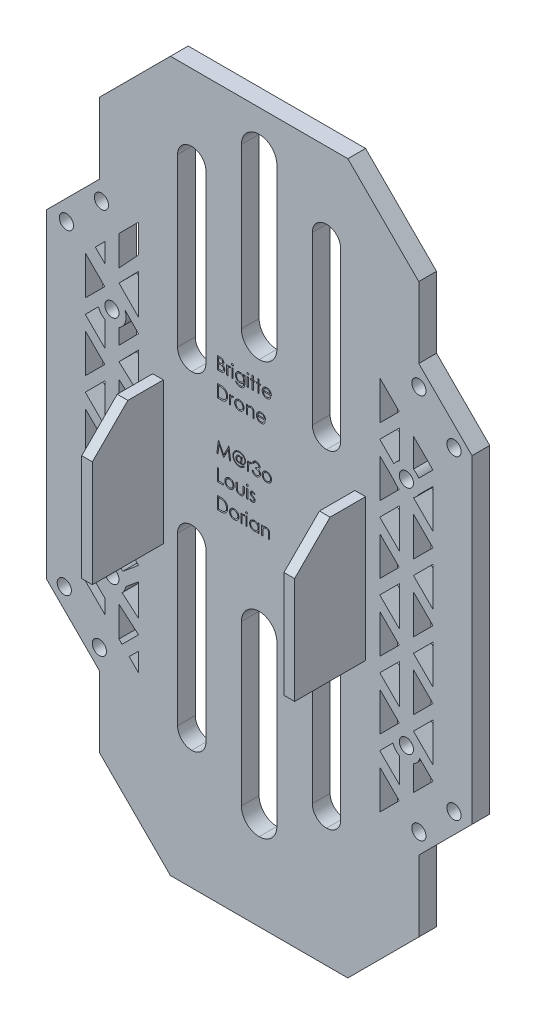
SolidWorks part; units mm, degrees
ref_plane "Plan de face" through (0, 0, 0) normal (0, 0, 1) x (1, 0, 0)
ref_plane "Plan de dessus" through (0, 0, 0) normal (0, 1, 0) x (1, 0, 0)
ref_plane "Plan de droite" through (0, 0, 0) normal (1, 0, 0) x (0, 0, -1)
sketch "Esquisse1" plane through (0, 0, 0) normal (0, 0, 1) x (1, 0, 0)
  line L0 (-41.0719, 30.2056) -> (78.9281, 30.2056)
  line L1 (78.9281, 30.2056) -> (78.9281, -89.7944)
  line L2 (78.9281, -89.7944) -> (-41.0719, -89.7944)
  line L3 (-41.0719, -89.7944) -> (-41.0719, 30.2056)
  dimension "D1" = 120
  dimension "D2" = 120
extrude "Boss.-Extru.2" add sketch "Esquisse1" along normal blind 5
sketch "Esquisse3" plane through (0, 0, 0) normal (0, 0, -1) x (-1, 0, 0)
sketch "Esquisse7" plane through (0, 0, 5) normal (0, 0, 1) x (1, 0, 0)
sketch "Esquisse9" plane through (0, 0, 5) normal (0, 0, 1) x (1, 0, 0)
  line L0 (-41.0719, -89.7944) -> (78.9281, -89.7944) construction
  line L1 (78.9281, -89.7944) -> (78.9281, 30.2056) construction
  circle A0 centre (-22.5719, -64.7944) radius 2
  circle A1 centre (-22.5719, 0.2056) radius 2
  circle A2 centre (60.4281, 0.2056) radius 2
  circle A3 centre (60.4281, -64.7944) radius 2
  dimension "D5" = 4
  dimension "D6" = 4
  dimension "D7" = 4
  dimension "D8" = 4
  dimension "D1" = 83
  dimension "D2" = 83
  dimension "D3" = 18.5
  dimension "D4" = 65
  dimension "D9" = 25
  dimension "D10" = 25
  dimension "D11" = 18.5
chamfer "Chanfrein5" distance 15 angle 45 1 edges at (78.9281, -89.7944, 2.5)
chamfer "Chanfrein6" distance 15 angle 45 1 edges at (78.9281, 30.2056, 2.5)
chamfer "Chanfrein7" distance 15 angle 45 1 edges at (-41.0719, 30.2056, 2.5)
chamfer "Chanfrein8" distance 15 angle 45 1 edges at (-41.0719, -89.7944, 2.5)
sketch "Esquisse21" plane through (0, -89.7944, 0) normal (0, -1, 0) x (-1, 0, 0)
  line L0 (26.0719, -5) -> (26.0719, 0)
  line L1 (26.0719, 0) -> (-63.9281, 0)
  line L2 (-63.9281, 0) -> (-63.9281, -5)
  line L3 (-63.9281, -5) -> (26.0719, -5)
extrude "Boss.-Extru.7" add sketch "Esquisse21" along normal blind 40
sketch "Esquisse22" plane through (0, 30.2056, 0) normal (0, 1, 0) x (1, 0, 0)
  line L0 (63.9281, -5) -> (63.9281, 0)
  line L1 (63.9281, 0) -> (-26.0719, 0) construction
  line L2 (63.9281, 0) -> (-26.0719, 0)
  line L3 (-26.0719, 0) -> (-26.0719, -5)
  line L4 (-26.0719, -5) -> (63.9281, -5)
extrude "Boss.-Extru.8" add sketch "Esquisse22" along normal blind 40
chamfer "Chanfrein23" distance 20 angle 45 4 edges at (-26.0719, -129.7944, 2.5) (63.9281, -129.7944, 2.5) (-26.0719, 70.2056, 2.5) (63.9281, 70.2056, 2.5)
sketch "Esquisse23" plane through (0, 0, 5) normal (0, 0, 1) x (1, 0, 0)
  line L0 (-41.0719, -74.7944) -> (-26.0719, -89.7944) construction
  line L1 (-26.0719, 30.2056) -> (-41.0719, 15.2056) construction
  line L3 (78.9281, 15.2056) -> (63.9281, 30.2056) construction
  line L5 (63.9281, -89.7944) -> (78.9281, -74.7944) construction
  circle A0 centre (-35.9963, -74.2132) radius 2
  circle A1 centre (-26.0968, -84.1127) radius 2
  circle A2 centre (-25.5241, 25.0966) radius 2
  circle A3 centre (-35.3901, 15.1637) radius 2
  circle A4 centre (63.9532, 24.5237) radius 2
  circle A5 centre (73.8527, 14.6242) radius 2
  circle A6 centre (63.9532, -84.1124) radius 2
  circle A7 centre (73.8527, -74.2129) radius 2
  dimension "D3" = 4
  dimension "D4" = 4
  dimension "D6" = 4
  dimension "D7" = 4
  dimension "D10" = 5.6818
  dimension "D15" = 4
  dimension "D16" = 4
  dimension "D19" = 14
  dimension "D23" = 4
  dimension "D24" = 4
  dimension "D1" = 4
  dimension "D2" = 4
  dimension "D5" = 14
  dimension "D8" = 14
  dimension "D9" = 4
  dimension "D11" = 5.682
  dimension "D12" = 5.109
  dimension "D13" = 14
  dimension "D14" = 4
  dimension "D17" = 4
  dimension "D18" = 5.682
  dimension "D20" = 4
  dimension "D21" = 5.682
  dimension "D22" = 4
extrude "Enlèv. mat.-Extru.1" cut sketch "Esquisse23" against normal blind 10
sketch "Esquisse24" plane through (0, 0, 5) normal (0, 0, 1) x (1, 0, 0)
  line L0 (63.9281, -89.7944) -> (78.9281, -74.7944) construction
  circle A0 centre (63.5389, -84.5268) radius 2.5407
  circle A1 centre (73.4383, -74.6273) radius 2.5147
  dimension "D1" = 4
  dimension "D2" = 4
  dimension "D3" = 14
  dimension "D4" = 5.282
sketch "Sketch1" plane through (0, 0, 5) normal (0, 0, 1) x (1, 0, 0)
  line L1 (13.9281, -107.7944) -> (23.9281, -107.7944)
  line L2 (13.9281, -107.7944) -> (13.9281, -52.7944)
  line L3 (13.9281, -52.7944) -> (23.9281, -52.7944)
  line L4 (23.9281, -107.7944) -> (23.9281, -52.7944)
  line L6 (43.9281, -129.7944) -> (-6.0719, -129.7944) construction
  dimension "D1" = 10
  dimension "D2" = 55
  dimension "D3" = 40
  dimension "D4" = 22
extrude "Cut-Extrude2" cut sketch "Sketch1" against normal blind 5 contours L2 L1 L4 L3
fillet "Fillet2" radius 5 1 edges at (13.9281, -107.7944, 2.5)
fillet "Fillet3" radius 5 3 edges at (13.9281, -52.7944, 2.5) (23.9281, -52.7944, 2.5) (23.9281, -107.7944, 2.5)
sketch "Sketch2" plane through (0, 0, 5) normal (0, 0, 1) x (1, 0, 0)
  line L0 (23.9281, -102.7944) -> (23.9281, -57.7944) construction
  line L1 (41.9281, -96.2103) -> (33.9281, -96.2103)
  line L2 (41.9281, -96.2103) -> (41.9281, -41.2103)
  line L3 (41.9281, -41.2103) -> (33.9281, -41.2103)
  line L4 (33.9281, -96.2103) -> (33.9281, -41.2103)
  line L5 (13.9281, -102.7944) -> (13.9281, -57.7944) construction
  line L6 (3.9281, -96.2103) -> (-4.0719, -96.2103)
  line L7 (3.9281, -96.2103) -> (3.9281, -41.2103)
  line L8 (3.9281, -41.2103) -> (-4.0719, -41.2103)
  line L9 (-4.0719, -96.2103) -> (-4.0719, -41.2103)
  dimension "D1" = 10
  dimension "D2" = 10
  dimension "D3" = 8
  dimension "D4" = 8
  dimension "D5" = 55
  dimension "D6" = 55
sketch "Sketch3" plane through (0, 0, 5) normal (0, 0, 1) x (1, 0, 0)
  line L0 (78.9281, -74.7944) -> (78.9281, 15.2056) construction
  line L1 (23.9281, 63.6661) -> (13.9281, 63.6661)
  line L2 (23.9281, 63.6661) -> (23.9281, 8.6661)
  line L3 (23.9281, 8.6661) -> (13.9281, 8.6661)
  line L4 (13.9281, 63.6661) -> (13.9281, 8.6661)
  dimension "D1" = 10
  dimension "D2" = 55
  dimension "D3" = 55
extrude "Cut-Extrude4" cut sketch "Sketch3" against normal blind 5
fillet "Fillet11" radius 5 4 edges at (13.9281, 63.6661, 2.5) (23.9281, 63.6661, 2.5) (23.9281, 8.6661, 2.5) (13.9281, 8.6661, 2.5)
extrude "Cut-Extrude5" cut sketch "Sketch2" against normal blind 8
sketch "Sketch4" plane through (0, 0, 5) normal (0, 0, 1) x (1, 0, 0)
  line L0 (13.9281, 58.6661) -> (13.9281, 13.6661) construction
  line L1 (-4.0719, 51.2056) -> (3.9281, 51.2056)
  line L2 (-4.0719, 51.2056) -> (-4.0719, -3.7944)
  line L3 (-4.0719, -3.7944) -> (3.9281, -3.7944)
  line L4 (3.9281, 51.2056) -> (3.9281, -3.7944)
  line L5 (33.9281, 51.2056) -> (41.9281, 51.2056)
  line L6 (33.9281, 51.2056) -> (33.9281, -3.7944)
  line L7 (33.9281, -3.7944) -> (41.9281, -3.7944)
  line L8 (41.9281, 51.2056) -> (41.9281, -3.7944)
  line L9 (23.9281, 13.6661) -> (23.9281, 58.6661) construction
  line L10 (-6.0719, 70.2056) -> (43.9281, 70.2056) construction
  dimension "D1" = 8
  dimension "D2" = 55
  dimension "D3" = 55
  dimension "D4" = 8
  dimension "D5" = 10
  dimension "D6" = 10
  dimension "D7" = 19
  dimension "D8" = 19
extrude "Cut-Extrude6" cut sketch "Sketch4" against normal blind 8
fillet "Fillet12" radius 4 4 edges at (33.9281, 51.2056, 2.5) (41.9281, 51.2056, 2.5) (41.9281, -3.7944, 2.5) (33.9281, -3.7944, 2.5)
fillet "Fillet13" radius 4 4 edges at (-4.0719, -3.7944, 2.5) (3.9281, -3.7944, 2.5) (-4.0719, 51.2056, 2.5) (3.9281, 51.2056, 2.5)
fillet "Fillet14" radius 4 4 edges at (3.9281, -41.2103, 2.5) (-4.0719, -41.2103, 2.5) (-4.0719, -96.2103, 2.5) (3.9281, -96.2103, 2.5)
fillet "Fillet15" radius 4 4 edges at (41.9281, -96.2103, 2.5) (33.9281, -96.2103, 2.5) (33.9281, -41.2103, 2.5) (41.9281, -41.2103, 2.5)
sketch "Sketch5" plane through (0, 0, 5) normal (0, 0, 1) x (1, 0, 0)
  line L0 (-6.0719, 70.2056) -> (43.9281, 70.2056) construction
  line L1 (-11.0719, -9.7944) -> (-8.0719, -9.7944)
  line L2 (-11.0719, -9.7944) -> (-11.0719, -49.7944)
  line L3 (-11.0719, -49.7944) -> (-8.0719, -49.7944)
  line L4 (-8.0719, -9.7944) -> (-8.0719, -49.7944)
  line L5 (45.9281, -9.7944) -> (48.9281, -9.7944)
  line L6 (45.9281, -9.7944) -> (45.9281, -49.7944)
  line L7 (45.9281, -49.7944) -> (48.9281, -49.7944)
  line L8 (48.9281, -9.7944) -> (48.9281, -49.7944)
  line L9 (-41.0719, 15.2056) -> (-41.0719, -74.7944) construction
  dimension "D1" = 40
  dimension "D2" = 40
  dimension "D3" = 80
  dimension "D4" = 80
  dimension "D5" = 3
  dimension "D6" = 3
  dimension "D7" = 54
  dimension "D8" = 30
extrude "Boss-Extrude1" add sketch "Sketch5" along normal blind 20
chamfer "Chamfer1" distance 10 angle 45 1 edges at (47.4281, -9.7944, 25)
chamfer "Chamfer2" distance 10 angle 45 1 edges at (-9.5719, -9.7944, 25)
extrude "Cut-Extrude7" cut sketch "Esquisse9" against normal blind 10
sketch "Sketch6" plane through (0, 0, 5) normal (0, 0, 1) x (1, 0, 0)
  line L0 (-15.0719, -120.7944) -> (-15.0719, 61.2056)
  line L1 (-26.0719, -109.7944) -> (-6.0719, -129.7944) construction
  line L2 (-6.0719, 70.2056) -> (-26.0719, 50.2056) construction
  line L3 (-30.0719, -85.7944) -> (-30.0719, 26.2056)
  line L4 (-41.0719, -74.7944) -> (-26.0719, -89.7944) construction
  line L5 (-26.0719, 30.2056) -> (-41.0719, 15.2056) construction
  line L6 (-41.0719, 15.2056) -> (-41.0719, -74.7944) construction
  line L7 (-15.0719, 17.2056) -> (-20.5719, 11.2719)
  line L8 (-20.5719, -115.2944) -> (-20.5719, 55.7056)
  line L9 (-24.5719, -53.8095) -> (-24.5719, 126.1905)
  line L10 (-24.5719, -53.8095) -> (-24.5719, -111.2944)
  line L11 (-15.0719, -84.7944) -> (-30.0719, -69.7944)
  line L12 (-15.0719, 25.2056) -> (-30.0719, 10.2056)
  line L13 (-15.0719, 13.2056) -> (-20.5719, 7.5964)
  line L14 (-20.5719, 7.5964) -> (-15.0719, 1.9874)
  line L15 (-20.5719, 7.5964) -> (-15.0719, 7.5964)
  line L16 (-15.0719, -6.0126) -> (-20.5719, -11.6216)
  line L17 (-20.5719, 3.5964) -> (-20.2132, 3.2306)
  line L18 (-19.2957, 2.2949) -> (-15.0719, -2.0126)
  line L19 (-15.0719, -2.0126) -> (-20.5719, -7.6216)
  line L20 (-20.5719, -11.6216) -> (-15.0719, -16.6452)
  line L21 (-20.5719, -15.9374) -> (-15.0719, -20.6452)
  line L22 (-15.0719, -20.6452) -> (-20.5719, -26.0772)
  line L23 (-15.0719, -24.6452) -> (-20.5719, -30.0772)
  line L24 (-20.5719, -30.0772) -> (-15.0719, -35.5772)
  line L25 (-20.5719, -34.0772) -> (-15.0719, -39.5772)
  line L26 (-15.0719, -39.5772) -> (-20.5719, -45.0772)
  line L27 (-20.5719, -49.0772) -> (-15.0719, -43.5772)
  line L28 (-20.5719, -49.0772) -> (-15.0719, -54.5772)
  line L29 (-20.5719, -53.0772) -> (-15.0719, -58.5772)
  line L30 (-15.0719, -58.5772) -> (-19.4924, -62.2416)
  line L31 (-15.0719, -62.5772) -> (-18.6413, -65.536)
  line L32 (-20.5719, -70.7698) -> (-15.0719, -75.5192)
  line L36 (-15.0719, -71.5192) -> (-19.6707, -67.5481)
  line L37 (-15.0719, -75.5192) -> (-19.7096, -80.1568)
  line L38 (-15.0719, -79.5192) -> (-17.7096, -82.1568)
  line L39 (-30.0719, 10.2056) -> (-24.5719, 4.7056)
  line L40 (-27.2435, 13.034) -> (-24.5719, 10.3625)
  line L41 (-24.5719, 4.7056) -> (-30.0719, 4.7056)
  line L43 (-24.5719, 4.7056) -> (-30.0719, -0.7944)
  line L45 (-30.0719, -65.7988) -> (-30.0719, -69.7944)
  line L46 (-30.0719, -4.7944) -> (-24.5719, -4.7944)
  line L47 (-30.0719, -4.7944) -> (-24.5719, -10.2944)
  line L48 (-30.0719, -8.7944) -> (-24.5719, -14.2944)
  line L49 (-24.5719, -14.2944) -> (-30.0719, -14.2944)
  line L50 (-24.5719, -14.2944) -> (-30.0719, -19.7944)
  line L51 (-24.5719, -18.2944) -> (-30.0719, -23.7944)
  line L52 (-30.0719, -23.7944) -> (-24.5719, -23.7944)
  line L53 (-30.0719, -23.7944) -> (-24.5719, -29.2944)
  line L54 (-30.0719, -27.7944) -> (-24.5719, -33.2944)
  line L55 (-24.5719, -33.2944) -> (-30.0719, -33.2944)
  line L56 (-24.5719, -33.2944) -> (-30.0719, -38.9521)
  line L57 (-24.5719, -37.2944) -> (-30.0719, -42.9521)
  line L58 (-30.0719, -42.9521) -> (-24.5719, -42.9521)
  line L59 (-30.0719, -42.9521) -> (-24.5719, -48.2988)
  line L60 (-30.0719, -46.9521) -> (-24.5719, -52.2988)
  line L61 (-24.5719, -52.2988) -> (-30.0719, -52.2988)
  line L62 (-24.5719, -52.2988) -> (-30.0719, -57.7988)
  line L63 (-24.5719, -56.2988) -> (-30.0719, -61.7988)
  line L64 (-30.0719, -61.7988) -> (-24.5719, -61.7988)
  line L66 (-30.0719, -65.7988) -> (-24.5719, -71.2988)
  line L67 (-30.0719, -61.7988) -> (-26.5352, -65.3356)
  line L68 (-24.5719, -75.2988) -> (-24.5697, -75.2966)
  line L69 (-30.0719, -4.7944) -> (-26.3592, -1.0816)
  line L70 (-30.0719, -69.7944) -> (-26.5697, -73.2966)
  circle A0 centre (-22.5719, -64.7944) radius 4
  circle A4 centre (-22.5719, 0.2056) radius 4
  dimension "D6" = 8
  dimension "D32" = 8
  dimension "D1" = 15
  dimension "D2" = 11
  dimension "D3" = 8
  dimension "D4" = 4
  dimension "D7" = 4
  dimension "D8" = 36
  dimension "D9" = 16
  dimension "D10" = 36
  dimension "D11" = 16
  dimension "D12" = 4
  dimension "D13" = 4
  dimension "D14" = 4
  dimension "D15" = 4
  dimension "D16" = 4
  dimension "D17" = 4
  dimension "D18" = 4
  dimension "D19" = 4
  dimension "D20" = 4
  dimension "D21" = 4
  dimension "D22" = 4
  dimension "D23" = 4
  dimension "D24" = 4
  dimension "D25" = 0
  dimension "D26" = 4
  dimension "D27" = 4
  dimension "D28" = 4
  dimension "D29" = 9.5
  dimension "D30" = 4
  dimension "D31" = 0
  dimension "D33" = 4
  dimension "D34" = 5.5
  dimension "D35" = 4
  dimension "D36" = 5.5
  dimension "D37" = 4
  dimension "D38" = 4
  dimension "D39" = 5.5
  dimension "D40" = 4
  dimension "D41" = 4
  dimension "D42" = 4
  dimension "D43" = 4
  dimension "D44" = 4
  dimension "D45" = 4
  dimension "D46" = 4
  dimension "D47" = 4
  dimension "D48" = 4
  dimension "D49" = 4
  dimension "D50" = 4
  dimension "D51" = 4
  dimension "D52" = 5.5
  dimension "D53" = 5.5
  dimension "D54" = 11
  dimension "D55" = 5.2752
extrude "Cut-Extrude8" cut sketch "Sketch6" against normal blind 10 contours L0 L38 L11 | L37 L32 L8 L11 | A0 L36 L0 L31 | A0 L30 L29 L8 | L27 L28 L0 | L26 L25 L8 | L23 L24 L0 | L22 L21 L8 | L16 L20 L0 | A4 L8 L19 L18 | L15 L14 L0 | L13 L15 L0 | L0 L12 L8 L7 | L12 L40 L9 region at (-15.9511, -82.1568, 5) region at (-18.6967, -75.6505, 5) region at (-16.6873, -67.0376, 5) region at (-18.6818, -58.1104, 5) region at (-16.9053, -49.0772, 5) region at (-18.7386, -39.5772, 5) region at (-16.9053, -30.0999, 5) region at (-18.7386, -20.8866, 5) region at (-16.9053, -11.4265, 5) region at (-18.288, -2.9591, 5) region at (-16.9053, 5.7267, 5) region at (-16.9053, 9.4661, 5) region at (-17.8461, 18.322, 5) region at (-25.4625, 13.034, 5)
sketch "Sketch7" plane through (0, 0, 5) normal (0, 0, 1) x (1, 0, 0)
extrude "Cut-Extrude9" cut sketch "Sketch6<3>" against normal blind 10 from offset 0 contours L12 L40 L9 | L41 L39 L3 | L43 L41 L3 | A4 L69 L46 L9 | L46 L47 L9 | L49 L48 L3 | L50 L49 L3 | L51 L52 L9 | L52 L53 L9 | L55 L54 L3 | L56 L55 L3 | L57 L58 L9 | L58 L59 L9 | L61 L60 L3 | L62 L61 L3 | A0 L10 L63 L64 | A0 L64 L67 | L10 L11 region at (-27.3219, -70.5466, 5) region at (-26.4228, -59.9472, 5) region at (-27.4757, -62.8923, 5) region at (-28.2386, -54.1321, 5) region at (-28.2386, -50.5165, 5) region at (-26.4053, -44.7343, 5) region at (-26.4053, -41.0662, 5) region at (-28.2386, -35.1803, 5) region at (-28.2386, -31.4611, 5) region at (-26.4053, -25.6277, 5) region at (-26.4053, -21.9611, 5) region at (-26.8378, -3.5511, 5) region at (-28.2386, -16.1277, 5) region at (-26.4053, -6.6277, 5) region at (-28.2386, -12.4611, 5) region at (-28.2386, 6.5389, 5) region at (-28.2386, 2.8723, 5) region at (-25.4625, 13.034, 5)
sketch "Sketch6<3>" plane through (0, 0, 5) normal (0, 0, 1) x (1, 0, 0) same geometry as "Sketch6"
sketch "Sketch9" plane through (0, 0, 5) normal (0, 0, 1) x (1, 0, 0)
  line L0 (78.9281, -74.7944) -> (78.9281, 15.2056) construction
  line L1 (58.4281, -60.2944) -> (52.9281, -60.2944)
  line L2 (43.9281, -129.7944) -> (63.9281, -109.7944) construction
  line L3 (62.4281, -111.2944) -> (62.4281, 51.7056)
  line L4 (63.9281, 50.2056) -> (43.9281, 70.2056) construction
  line L5 (58.4281, -115.2944) -> (58.4281, 55.7056)
  line L6 (67.9281, -85.7944) -> (67.9281, 26.2056)
  line L7 (63.9281, -89.7944) -> (78.9281, -74.7944) construction
  line L8 (78.9281, 15.2056) -> (63.9281, 30.2056) construction
  line L9 (52.9281, -120.7944) -> (52.9281, 61.2056)
  line L10 (52.9281, -120.7944) -> (52.9281, -84.7944)
  line L11 (67.9281, -85.7944) -> (67.9281, -69.7944)
  line L12 (52.9281, -84.7944) -> (67.9281, -69.7944)
  line L13 (52.9281, -79.2944) -> (58.4281, -79.2944)
  line L14 (58.4281, -79.2944) -> (52.9281, -73.7944)
  line L15 (52.9281, -69.7944) -> (58.4281, -75.2944)
  line L16 (52.9281, -69.7944) -> (58.4281, -69.7944)
  line L17 (52.9281, -69.7944) -> (58.4281, -64.2944)
  line L18 (52.9281, -65.7944) -> (58.4281, -60.2944)
  line L19 (58.4281, -60.2944) -> (52.9281, -54.7944)
  line L20 (52.9281, -50.7944) -> (58.4281, -56.2944)
  line L21 (52.9281, -50.7944) -> (58.4281, -50.7944)
  line L22 (52.9281, -50.7944) -> (58.4281, -45.2944)
  line L23 (52.9281, -46.7944) -> (58.4281, -41.2944)
  line L24 (58.4281, -41.2944) -> (52.9281, -41.2944)
  line L25 (58.4281, -41.2944) -> (52.9281, -35.7944)
  line L26 (52.9281, -31.7944) -> (58.4281, -37.2944)
  line L27 (52.9281, -31.7944) -> (58.4281, -31.7944)
  line L28 (52.9281, -31.7944) -> (58.4281, -26.2944)
  line L29 (52.9281, -27.7944) -> (58.4281, -22.2944)
  line L30 (58.4281, -22.2944) -> (52.9281, -22.2944)
  line L31 (58.4281, -22.2944) -> (52.9281, -16.7944)
  line L32 (52.9281, -12.7944) -> (58.4281, -18.2944)
  line L33 (52.9281, -12.7944) -> (58.4281, -12.7944)
  line L34 (52.9281, -12.7944) -> (58.4281, -7.2944)
  line L35 (52.9281, -8.7944) -> (58.4281, -3.2944)
  line L36 (58.4281, -3.2944) -> (52.9281, -3.2944)
  line L37 (58.4281, -3.2944) -> (52.9281, 2.2056)
  line L38 (58.4281, 0.7056) -> (52.9281, 6.2056)
  line L39 (52.9281, 6.2056) -> (58.4281, 6.2056)
  line L40 (52.9281, 6.2056) -> (58.4281, 11.7056)
  line L41 (52.9281, 10.2056) -> (58.4281, 15.7056)
  line L42 (52.9281, 61.2056) -> (52.9281, 25.2056)
  line L43 (67.9281, 26.2056) -> (67.9281, 10.2056)
  line L44 (52.9281, 25.2056) -> (67.9281, 10.2056)
  line L45 (58.4281, 15.7056) -> (52.9281, 15.7056)
  line L46 (58.4281, 15.7056) -> (52.9281, 21.2056)
  line L47 (58.4281, 19.7056) -> (52.9281, 25.2056)
  line L48 (67.9281, -69.7944) -> (62.4281, -69.7944)
  line L49 (67.9281, -69.7944) -> (62.4281, -64.2944)
  line L50 (67.9281, -65.7944) -> (62.4281, -60.2944)
  line L51 (62.4281, -60.2944) -> (67.9281, -60.2944)
  line L52 (62.4281, -60.2944) -> (67.9281, -54.7944)
  line L53 (62.4281, -56.2944) -> (67.9281, -50.7944)
  line L54 (67.9281, -50.7944) -> (62.4281, -50.7944)
  line L55 (67.9281, -50.7944) -> (62.4281, -45.2944)
  line L56 (62.4281, -41.2944) -> (67.9281, -46.7944)
  line L57 (62.4281, -41.2944) -> (67.9281, -41.2944)
  line L58 (62.4281, -41.2944) -> (67.9281, -35.7944)
  line L59 (62.4281, -37.2944) -> (67.9281, -31.7944)
  line L60 (67.9281, -31.7944) -> (62.4281, -31.7944)
  line L61 (67.9281, -31.7944) -> (62.4281, -26.2944)
  line L62 (67.9281, -27.7944) -> (62.4281, -22.2944)
  line L63 (62.4281, -22.2944) -> (67.9281, -22.2944)
  line L64 (62.4281, -22.2944) -> (67.9281, -16.7944)
  line L65 (62.4281, -18.2944) -> (67.9281, -12.7944)
  line L66 (67.9281, -12.7944) -> (62.4281, -12.7944)
  line L67 (67.9281, -12.7944) -> (62.4281, -7.2944)
  line L68 (67.9281, -8.7944) -> (62.4281, -3.2944)
  line L69 (62.4281, -3.2944) -> (67.9281, -3.2944)
  line L70 (62.4281, -3.2944) -> (67.9281, 2.2056)
  line L71 (62.4281, 0.7056) -> (67.9281, 6.2056)
  line L72 (67.9281, 6.2056) -> (62.4281, 6.2056)
  line L73 (67.9281, 6.2056) -> (62.4281, 11.7056)
  circle A0 centre (60.4281, -64.7944) radius 4
  circle A1 centre (60.4281, 0.2056) radius 4
  dimension "D12" = 8
  dimension "D13" = 8
  dimension "D1" = 11
  dimension "D2" = 4
  dimension "D3" = 5.5
  dimension "D4" = 5.5
  dimension "D5" = 36
  dimension "D6" = 16
  dimension "D7" = 5.5
  dimension "D8" = 4
  dimension "D9" = 5.5
  dimension "D10" = 4
  dimension "D11" = 5.5
  dimension "D14" = 4
  dimension "D15" = 4
  dimension "D16" = 5.5
  dimension "D17" = 5.5
  dimension "D18" = 5.5
  dimension "D19" = 4
  dimension "D20" = 4
  dimension "D21" = 5.5
  dimension "D22" = 5.5
  dimension "D23" = 4
  dimension "D24" = 4
  dimension "D25" = 5.5
  dimension "D26" = 5.5
  dimension "D27" = 4
  dimension "D28" = 4
  dimension "D29" = 5.5
  dimension "D30" = 4
  dimension "D31" = 4
  dimension "D32" = 5.5
  dimension "D33" = 4
  dimension "D34" = 4
  dimension "D35" = 5.5
  dimension "D36" = 4
  dimension "D37" = 4
  dimension "D38" = 5.5
  dimension "D39" = 4
  dimension "D40" = 4
  dimension "D41" = 5.5
  dimension "D42" = 4
  dimension "D43" = 4
  dimension "D44" = 36
  dimension "D45" = 5.5
  dimension "D46" = 4
  dimension "D47" = 4
  dimension "D48" = 5.5
  dimension "D49" = 4
  dimension "D50" = 4
  dimension "D51" = 5.5
  dimension "D52" = 4
  dimension "D53" = 4
  dimension "D54" = 5.5
  dimension "D55" = 4
  dimension "D56" = 4
  dimension "D57" = 4
  dimension "D58" = 4
  dimension "D59" = 4
  dimension "D60" = 5.5
  dimension "D61" = 4
  dimension "D62" = 5.5
  dimension "D63" = 4
  dimension "D64" = 4
  dimension "D65" = 5.5
  dimension "D66" = 4
  dimension "D67" = 4
  dimension "D68" = 5.5
  dimension "D69" = 4
  dimension "D70" = 4
  dimension "D71" = 4
  dimension "D72" = 5.5
extrude "Cut-Extrude10" cut sketch "Sketch9" against normal blind 10 contours L13 L14 L9 | L16 L15 L5 | A0 L17 L16 L5 | L9 L18 L1 | L1 L19 L9 | L22 L21 L5 | L21 L20 L5 | L23 L24 L9 | L24 L25 L9 | L27 L26 L5 | L28 L27 L5 | L30 L31 L9 | L29 L30 L9 | L33 L32 L5 | L34 L33 L5 | A1 L37 L9 L36 | L35 L36 L9 | L40 L39 L5 | A1 L5 L39 L38 | L41 L45 L9 | L45 L46 L9 | L13 L9 L12 | L72 L73 L3 | A1 L71 L72 L3 | A1 L70 L69 L6 | L69 L68 L6 | L66 L67 L3 | L65 L66 L3 | L64 L63 L6 | L63 L62 L6 | L60 L61 L3 | L59 L60 L3 | L58 L57 L6 | L57 L56 L6 | L54 L55 L3 | L53 L54 L3 | L52 L51 L6 | L51 L50 L6 | A0 L3 L48 L49 | L12 L48 L3 region at (54.7614, -62.1277, 5) region at (54.7614, -58.4611, 5) region at (56.5947, -52.6277, 5) region at (56.5947, -48.9611, 5) region at (56.1622, -68.5511, 5) region at (56.5947, -71.6277, 5) region at (54.7614, -43.1277, 5) region at (66.0947, -62.1277, 5) region at (66.0947, -58.4611, 5) region at (54.7614, -77.4611, 5) region at (54.7614, -39.4611, 5) region at (64.6939, -68.5511, 5) region at (64.2614, -52.6277, 5) region at (54.7614, -81.1277, 5) region at (56.5947, -33.6277, 5) region at (64.2614, -71.6277, 5) region at (64.2614, -48.9611, 5) region at (56.5947, -29.9611, 5) region at (66.0947, -43.1277, 5) region at (54.7614, -24.1277, 5) region at (66.0947, -39.4611, 5) region at (54.7614, -20.4611, 5) region at (64.2614, -33.6277, 5) region at (56.5947, -14.6277, 5) region at (64.2614, -29.9611, 5) region at (56.5947, -10.9611, 5) region at (66.0947, -24.1277, 5) region at (54.7614, -5.1277, 5) region at (66.0947, -20.4611, 5) region at (54.7347, -1.4507, 5) region at (64.2614, -14.6277, 5) region at (64.2614, -10.9611, 5) region at (56.3481, 4.7696, 5) region at (56.5947, 8.0389, 5) region at (66.0947, -5.1277, 5) region at (66.1214, -1.4507, 5) region at (54.7614, 13.8723, 5) region at (64.5081, 4.7696, 5) region at (54.7614, 17.5389, 5) region at (64.2614, 8.0389, 5)
sketch "Sketch10" plane through (0, 0, 5) normal (0, 0, 1) x (1, 0, 0)
  text T0 "Brigitte\r\nDrone\r\n\r\nM@r3o\r\nLouis\r\nDorian"
extrude "Cut-Extrude11" cut sketch "Sketch10" against normal blind 2
